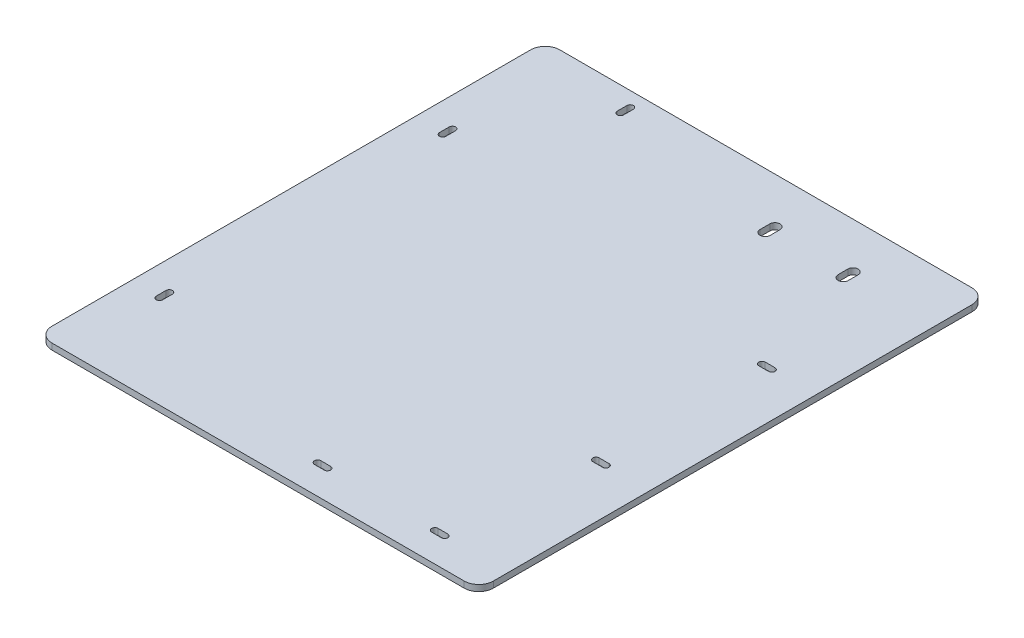
SolidWorks part; units mm, degrees
ref_plane "Front Plane" through (0, 0, 0) normal (0, 0, 1) x (1, 0, 0)
ref_plane "Top Plane" through (0, 0, 0) normal (0, 1, 0) x (1, 0, 0)
ref_plane "Right Plane" through (0, 0, 0) normal (1, 0, 0) x (0, 0, -1)
sketch "Sketch1" plane through (0, 0, 0) normal (0, 1, 0) x (1, 0, 0)
  line L0 (28, 104.1) -> (68, 104.1) construction
  line L1 (-113, -130) -> (113, -130)
  line L2 (-113, -130) -> (-113, 130)
  line L3 (-113, 130) -> (113, 130)
  line L4 (113, -130) -> (113, 130)
  line L5 (-113, -130) -> (113, 130) construction
  line L6 (-113, 130) -> (113, -130) construction
  line L7 (18, -115) -> (78, -115) construction
  line L8 (-98, 65) -> (-98, -80) construction
  line L9 (88, 42.5) -> (88, -42.5) construction
  line L10 (28, 106.6) -> (28, 101.6) construction
  line L11 (30.6, 106.6) -> (30.6, 101.6)
  line L12 (25.4, 106.6) -> (25.4, 101.6)
  line L13 (68, 106.6) -> (68, 101.6) construction
  line L14 (70.6, 106.6) -> (70.6, 101.6)
  line L15 (65.4, 106.6) -> (65.4, 101.6)
  line L16 (-98, 67.5) -> (-98, 62.5) construction
  line L17 (-96.35, 67.5) -> (-96.35, 62.5)
  line L18 (-99.65, 67.5) -> (-99.65, 62.5)
  line L19 (85.5, 42.5) -> (90.5, 42.5) construction
  line L20 (85.5, 44.15) -> (90.5, 44.15)
  line L21 (85.5, 40.85) -> (90.5, 40.85)
  line L22 (85.5, -42.5) -> (90.5, -42.5) construction
  line L23 (85.5, -40.85) -> (90.5, -40.85)
  line L24 (85.5, -44.15) -> (90.5, -44.15)
  line L25 (15.5, -115) -> (20.5, -115) construction
  line L26 (15.5, -113.35) -> (20.5, -113.35)
  line L27 (15.5, -116.65) -> (20.5, -116.65)
  line L28 (80.5, -115) -> (75.5, -115) construction
  line L29 (80.5, -116.65) -> (75.5, -116.65)
  line L30 (80.5, -113.35) -> (75.5, -113.35)
  line L31 (-98, -77.5) -> (-98, -82.5) construction
  line L32 (-96.35, -77.5) -> (-96.35, -82.5)
  line L33 (-99.65, -77.5) -> (-99.65, -82.5)
  line L34 (-62, 117.5) -> (-62, 122.5) construction
  line L35 (-63.65, 117.5) -> (-63.65, 122.5)
  line L36 (-60.35, 117.5) -> (-60.35, 122.5)
  arc A0 (30.6, 106.6) -> (25.4, 106.6) centre (28, 106.6) ccw
  arc A1 (25.4, 101.6) -> (30.6, 101.6) centre (28, 101.6) ccw
  arc A2 (70.6, 106.6) -> (65.4, 106.6) centre (68, 106.6) ccw
  arc A3 (65.4, 101.6) -> (70.6, 101.6) centre (68, 101.6) ccw
  arc A4 (-96.35, 67.5) -> (-99.65, 67.5) centre (-98, 67.5) ccw
  arc A5 (-99.65, 62.5) -> (-96.35, 62.5) centre (-98, 62.5) ccw
  arc A6 (85.5, 44.15) -> (85.5, 40.85) centre (85.5, 42.5) ccw
  arc A7 (90.5, 40.85) -> (90.5, 44.15) centre (90.5, 42.5) ccw
  arc A8 (85.5, -40.85) -> (85.5, -44.15) centre (85.5, -42.5) ccw
  arc A9 (90.5, -44.15) -> (90.5, -40.85) centre (90.5, -42.5) ccw
  arc A10 (15.5, -113.35) -> (15.5, -116.65) centre (15.5, -115) ccw
  arc A11 (20.5, -116.65) -> (20.5, -113.35) centre (20.5, -115) ccw
  arc A12 (80.5, -116.65) -> (80.5, -113.35) centre (80.5, -115) ccw
  arc A13 (75.5, -113.35) -> (75.5, -116.65) centre (75.5, -115) ccw
  arc A14 (-96.35, -77.5) -> (-99.65, -77.5) centre (-98, -77.5) ccw
  arc A15 (-99.65, -82.5) -> (-96.35, -82.5) centre (-98, -82.5) ccw
  arc A16 (-63.65, 117.5) -> (-60.35, 117.5) centre (-62, 117.5) ccw
  arc A17 (-60.35, 122.5) -> (-63.65, 122.5) centre (-62, 122.5) ccw
  point P0 (0, 0)
  point P6 (28, 104.1)
  point P7 (68, 104.1)
  point P8 (18, -115)
  point P9 (78, -115)
  point P10 (-98, 65)
  point P11 (-98, -80)
  point P12 (88, 42.5)
  point P13 (88, -42.5)
  point P20 (88, 0)
  point P21 (48, 104.1)
  point P24 (28, 104.1)
  point P30 (68, 104.1)
  point P39 (-98, 65)
  point P47 (88, 42.5)
  point P53 (88, -42.5)
  point P61 (18, -115)
  point P67 (78, -115)
  point P74 (-98, -80)
  point P81 (-62, 120)
  point P87 (0, 0)
  point P89 (48, -115)
  dimension "D7" = 1.65
  dimension "D9" = 2.6
  dimension "D1" = 40
  dimension "D2" = 145
  dimension "D3" = 60
  dimension "D4" = 219.1
  dimension "D5" = 260
  dimension "D6" = 15
  dimension "D8" = 5
  dimension "D10" = 5
  dimension "D11" = 226
  dimension "D12" = 15
  dimension "D13" = 50
  dimension "D14" = 131
  dimension "D15" = 250
  dimension "D16" = 80
  dimension "D17" = 85
  dimension "D18" = 40
extrude "Boss-Extrude1" add sketch "Sketch1" along normal blind 3.175
fillet "Fillet1" radius 7.5 4 edges at (113, 1.5875, -130) (113, 1.5875, 130) (-113, 1.5875, 130) (-113, 1.5875, -130)
sketch "Sketch3" plane through (0, 3.175, 0) normal (0, 1, 0) x (1, 0, 0)
  line L0 (15.5, -115) -> (20.5, -115) construction
  circle A0 centre (18, -115) radius 1.65 construction
  arc A1 (15.5, -113.35) -> (15.5, -116.65) centre (15.5, -115) ccw construction
  arc A2 (20.5, -116.65) -> (20.5, -113.35) centre (20.5, -115) ccw construction
  point P2 (0, 0)
  point P6 (18, -115)
  point P9 (0, 0)
  point P13 (0, 0)
